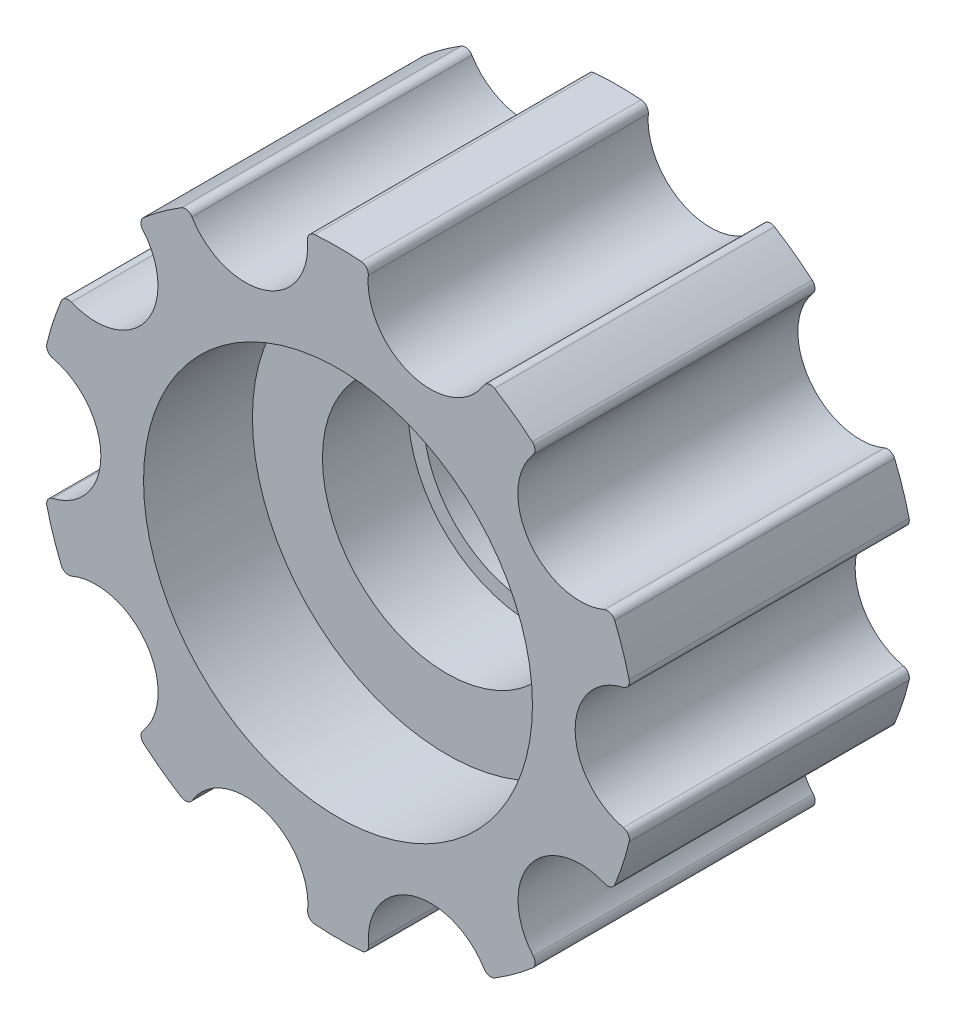
SolidWorks part; units mm, degrees
ref_plane "Front Plane" through (0, 0, 0) normal (0, 0, 1) x (1, 0, 0)
ref_plane "Top Plane" through (0, 0, 0) normal (0, 1, 0) x (1, 0, 0)
ref_plane "Right Plane" through (0, 0, 0) normal (1, 0, 0) x (0, 0, -1)
sketch "Sprocket" plane through (-521.3339, -864.335, -1401.844) normal (0, 0, 1) x (1, 0, 0)
  arc A8 (502.6212, 859.8188) -> (503.5468, 856.9742) centre (521.3339, 864.335) ccw
  arc A9 (502.9935, 860.4231) -> (502.6212, 859.8188) centre (503.1072, 859.9362) ccw
  arc A10 (503.5468, 856.9742) -> (504.2034, 856.7048) centre (504.0088, 857.1653) ccw
  arc A11 (504.1968, 871.9504) -> (503.5404, 871.6804) centre (504.0026, 871.4896) ccw
  arc A12 (503.5404, 871.6804) -> (502.6172, 868.8349) centre (521.3339, 864.335) ccw
  arc A13 (502.6172, 868.8349) -> (502.9901, 868.2311) centre (503.1034, 868.7181) ccw
  arc A14 (511.9459, 880.5689) -> (511.2562, 880.7363) centre (511.518, 880.3103) ccw
  arc A15 (511.2562, 880.7363) -> (508.8368, 878.9769) centre (521.3339, 864.335) ccw
  arc A16 (508.8368, 878.9769) -> (508.7835, 878.2692) centre (509.1614, 878.5966) ccw
  arc A17 (523.2809, 882.9866) -> (522.8213, 883.5275) centre (522.7827, 883.029) ccw
  arc A18 (522.8213, 883.5275) -> (519.8298, 883.5262) centre (521.3339, 864.335) ccw
  arc A19 (519.8298, 883.5262) -> (519.3707, 882.9849) centre (519.8689, 883.0277) ccw
  arc A20 (533.8722, 878.2801) -> (533.8183, 878.9877) centre (533.494, 878.6072) ccw
  arc A21 (533.8183, 878.9877) -> (531.3973, 880.7451) centre (521.3339, 864.335) ccw
  arc A22 (531.3973, 880.7451) -> (530.7078, 880.577) centre (531.136, 880.3188) ccw
  arc A23 (539.6743, 868.247) -> (540.0466, 868.8512) centre (539.5606, 868.7339) ccw
  arc A24 (540.0466, 868.8512) -> (539.121, 871.6959) centre (521.3339, 864.335) ccw
  arc A25 (539.121, 871.6959) -> (538.4644, 871.9653) centre (538.659, 871.5047) ccw
  arc A26 (538.471, 856.7196) -> (539.1274, 856.9896) centre (538.6652, 857.1804) ccw
  arc A27 (539.1274, 856.9896) -> (540.0506, 859.8351) centre (521.3339, 864.335) ccw
  arc A28 (540.0506, 859.8351) -> (539.6777, 860.439) centre (539.5644, 859.952) ccw
  arc A29 (530.7219, 848.1011) -> (531.4116, 847.9337) centre (531.1498, 848.3597) ccw
  arc A30 (531.4116, 847.9337) -> (533.831, 849.6931) centre (521.3339, 864.335) ccw
  arc A31 (533.831, 849.6931) -> (533.8843, 850.4008) centre (533.5064, 850.0734) ccw
  arc A32 (519.3869, 845.6834) -> (519.8465, 845.1426) centre (519.8851, 845.6411) ccw
  arc A33 (519.8465, 845.1426) -> (522.838, 845.1439) centre (521.3339, 864.335) ccw
  arc A34 (522.838, 845.1439) -> (523.2971, 845.6851) centre (522.7989, 845.6423) ccw
  arc A35 (508.7956, 850.39) -> (508.8495, 849.6823) centre (509.1738, 850.0629) ccw
  arc A36 (508.8495, 849.6823) -> (511.2705, 847.925) centre (521.3339, 864.335) ccw
  arc A37 (511.2705, 847.925) -> (511.96, 848.093) centre (511.5318, 848.3512) ccw
  arc A38 (504.1968, 871.9504) -> (508.7835, 878.2692) centre (505.7538, 875.6443) ccw
  arc A39 (502.9901, 868.2311) -> (502.9935, 860.4231) centre (502.0819, 864.3267) cw
  arc A40 (504.2034, 856.7048) -> (508.7956, 850.39) centre (505.7636, 853.0122) cw
  arc A41 (511.96, 848.093) -> (519.3869, 845.6834) centre (515.3927, 846.0227) cw
  arc A42 (530.7219, 848.1011) -> (523.2971, 845.6851) centre (527.291, 846.0279) ccw
  arc A43 (538.471, 856.7196) -> (533.8843, 850.4008) centre (536.914, 853.0258) ccw
  arc A44 (539.6743, 868.247) -> (539.6777, 860.439) centre (540.5859, 864.3434) ccw
  arc A45 (533.8722, 878.2801) -> (538.4644, 871.9653) centre (536.9041, 875.6578) ccw
  arc A46 (523.2809, 882.9866) -> (530.7078, 880.577) centre (527.2751, 882.6473) ccw
  arc A47 (511.9459, 880.5689) -> (519.3707, 882.9849) centre (515.3768, 882.6421) ccw
  dimension "D3" = 38.5
  dimension "D4" = 1
  dimension "D5" = 1
extrude "Sproket" add sketch "Sprocket" along normal blind 9 contours A44 A28 A27 A26 A43 A31 A30 A29 A42 A34 A33 A32 A41 A37 A36 A35 A40 A10 A8 A9 A39 A13 A12 A11 A38 A16 A15 A14 A47 A19 A18 A17 A46 A22 A21 A20 A45 A25 A24 A23
sketch "Sketch3" plane through (0, 0, -1392.844) normal (0, 0, 1) x (1, 0, 0)
  circle A0 centre (0, 0) radius 12.5
  dimension "D1" = 25
extrude "Cut-Extrude1" cut sketch "Sketch3" against normal blind 7
mirror "Mirror1" about plane through (9.1133, 2.1994, -1401.844) normal (0, 0, 1) of "Sproket", "Cut-Extrude1"
ref_axis "Wheel_Axis" through (0, 0, -1413.4135) along (0, 0, 1)
sketch "Sketch4" plane through (0, 0, -1403.844) normal (0, 0, -1) x (-1, 0, 0)
  circle A0 centre (0, 0) radius 10
  circle A1 centre (0, 0) radius 7
  dimension "D1" = 14
  dimension "D2" = 20
extrude "Boss-Extrude1" add sketch "Sketch4" along normal blind 7
sketch "Sketch5" plane through (0, 0, -1399.844) normal (0, 0, 1) x (1, 0, 0)
  circle A0 centre (0, 0) radius 8
  dimension "D1" = 16
extrude "Cut-Extrude2" cut sketch "Sketch5" against normal blind 5.5
